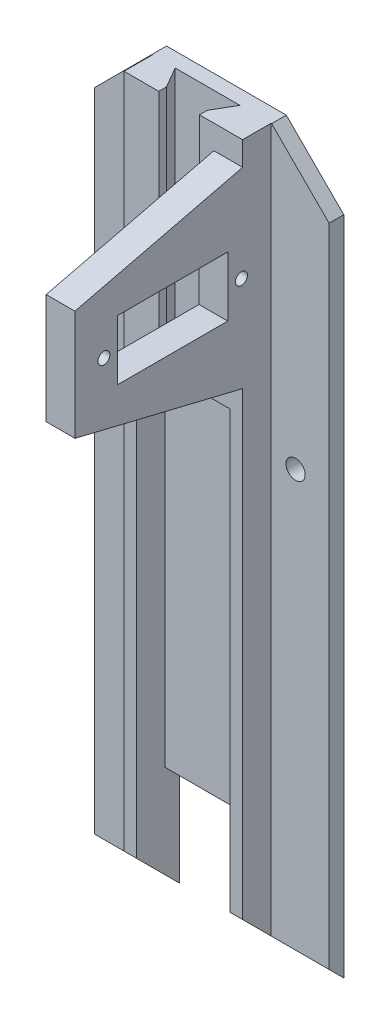
SolidWorks part; units mm, degrees
ref_plane "Front Plane" through (0, 0, 0) normal (0, 0, 1) x (1, 0, 0)
ref_plane "Top Plane" through (0, 0, 0) normal (0, 1, 0) x (1, 0, 0)
ref_plane "Right Plane" through (0, 0, 0) normal (1, 0, 0) x (0, 0, -1)
sketch "Sketch1" plane through (0, 0, 0) normal (0, 0, 1) x (1, 0, 0)
  line L1 (-11.5, 38) -> (11.5, 38)
  line L2 (-11.5, 38) -> (-11.5, -38)
  line L3 (-11.5, -38) -> (11.5, -38)
  line L4 (11.5, 38) -> (11.5, -38)
  line L5 (-11.5, 38) -> (11.5, -38) construction
  line L6 (-11.5, -38) -> (11.5, 38) construction
  point P0 (0, 0)
  dimension "D1" = 76
  dimension "D2" = 23
extrude "Boss-Extrude1" add sketch "Sketch1" along normal blind 8
sketch "Sketch2" plane through (0, -38, 0) normal (0, -1, 0) x (1, 0, 0)
  line L9 (-4.25, 8) -> (4.25, 8)
  line L13 (0, 0) -> (0, 8) construction
  line L14 (-11.5, 8) -> (11.5, 8) construction
  line L15 (-4.25, 8) -> (-4.25, 6.4001)
  line L16 (4.25, 8) -> (4.25, 6.4001)
  line L17 (-6.75, 2.07) -> (6.75, 2.07)
  line L18 (-6.75, 2.07) -> (-4.25, 6.4001)
  line L19 (6.75, 2.07) -> (4.25, 6.4001)
  line L21 (-11.5, 0) -> (11.5, 0) construction
  point P4 (0, 8)
  point P10 (0, 2.07)
  dimension "D1" = 8.5
  dimension "D2" = 2.07
  dimension "D3" = 60
  dimension "D4" = 13.5
extrude "Cut-Extrude2" cut sketch "Sketch2" against normal through all both and the other way through all contours L19 L16 L9 L15 L18 L17
sketch "Sketch3" plane through (0, -38, 0) normal (0, -1, 0) x (1, 0, 0)
  line L0 (4.25, 8) -> (13.25, 8)
  line L1 (13.25, 8) -> (13.25, 0)
  line L2 (13.25, 0) -> (11.5, 0)
  line L3 (11.5, 0) -> (11.5, 8)
  line M7 (11.5, 0) -> (11.5, 8)
  dimension "D1" = 9
extrude "Boss-Extrude2" add sketch "Sketch3" against normal blind 76 contours L2 L1 L0 M7 region at (12.375, -38, 4)
sketch "Sketch4" plane through (13.25, 0, 0) normal (1, 0, 0) x (0, 0, -1)
  line L0 (-8, 38) -> (-8, 33)
  line L6 (-8, 38) -> (-8, -38) construction
  line L7 (-8, 33) -> (-43, 24.5)
  line L8 (-43, 24.5) -> (-43, 1.5)
  line L9 (-43, 1.5) -> (-8, -7)
  line L10 (-8, 33) -> (-8, -7)
  point P5 (-43, 13)
  point P10 (-8, 13)
  line M13 (-8, 38) -> (-8, -38)
  dimension "D1" = 5
  dimension "D2" = 23
  dimension "D3" = 35
  dimension "D4" = 40
extrude "Boss-Extrude3" add sketch "Sketch4" against normal blind 6 contours L8 L9 L7 M13 region at (13.25, 13, 23.9259)
sketch "Sketch5" plane through (13.25, 0, 0) normal (1, 0, 0) x (0, 0, -1)
  line L0 (-43, 24.5) -> (-43, 1.5) construction
  line L1 (-34.1, 19.25) -> (-11.1, 19.25)
  line L2 (-34.1, 19.25) -> (-34.1, 6.75)
  line L3 (-34.1, 6.75) -> (-11.1, 6.75)
  line L4 (-11.1, 19.25) -> (-11.1, 6.75)
  line L5 (-34.1, 19.25) -> (-11.1, 6.75) construction
  line L6 (-34.1, 6.75) -> (-11.1, 19.25) construction
  point P0 (-22.6, 13)
  point P7 (-43, 13)
  dimension "D1" = 23
  dimension "D2" = 12.5
  dimension "D3" = 8.9
extrude "Cut-Extrude3" cut sketch "Sketch5" against normal blind 8
sketch "Sketch6" plane through (13.25, 0, 0) normal (1, 0, 0) x (0, 0, -1)
  line L0 (-43, 13) -> (0, 13) construction
  line L1 (-39.8073, 15.003) -> (-34.1, 15.003)
  line L2 (-39.8073, 15.003) -> (-39.8073, 10.997)
  line L3 (-39.8073, 10.997) -> (-34.1, 10.997)
  line L4 (-34.1, 15.003) -> (-34.1, 10.997)
  line L5 (-39.8073, 15.003) -> (-34.1, 10.997) construction
  line L6 (-39.8073, 10.997) -> (-34.1, 15.003) construction
  line L7 (-43, 24.5) -> (-43, 1.5) construction
  line L8 (0, 38) -> (0, -38) construction
  line L9 (-34.1, 19.25) -> (-34.1, 6.75) construction
  line L10 (-22.6, 19.25) -> (-22.6, 6.75) construction
  line L11 (-11.1, 19.25) -> (-34.1, 19.25) construction
  line L12 (-34.1, 6.75) -> (-11.1, 6.75) construction
  line L13 (-11.1, 15.003) -> (-11.1, 10.997)
  line L14 (-5.3927, 15.003) -> (-11.1, 15.003)
  line L15 (-5.3927, 15.003) -> (-5.3927, 10.997)
  line L16 (-5.3927, 10.997) -> (-11.1, 10.997)
  circle A0 centre (-36.9537, 13) radius 1.25
  circle A1 centre (-8.2463, 13) radius 1.25
  point P0 (-36.9537, 13)
  dimension "D2" = 2.5
  dimension "D1" = 0
extrude "Cut-Extrude4" cut sketch "Sketch6" against normal blind 4 contours A0 | A1
sketch "Sketch7" plane through (0, 0, 0) normal (0, 0, -1) x (-1, 0, 0)
  line L0 (-0.875, 38) -> (-0.875, 23.9968) construction
  line L1 (-13.25, 38) -> (11.5, 38) construction
  line L3 (11.5, 31) -> (17.511, 31) construction
  line L4 (11.5, 38) -> (11.5, -38) construction
  line L5 (11.5, 35) -> (17.511, 35)
  line L7 (11.5, 0) -> (-13.25, 0) construction
  line L8 (-13.25, 38) -> (-13.25, -38) construction
  line L9 (-13.05, 31) -> (-19.061, 31) construction
  line L10 (-13.05, 35) -> (-19.061, 35)
  line L11 (-13.05, 27) -> (-19.061, 27)
  line L12 (-13.05, -31) -> (-19.261, -31) construction
  line L13 (-13.05, -35) -> (-19.061, -35)
  line L14 (-13.05, -27) -> (-19.061, -27)
  line L15 (11.5, -31) -> (17.511, -31) construction
  line L16 (11.5, -35) -> (17.511, -35)
  line L17 (11.5, -27) -> (17.511, -27)
  line L18 (11.5, 35) -> (11.5, 27)
  line L19 (-13.05, 35) -> (-13.05, 27)
  line L20 (-13.05, -27) -> (-13.05, -35)
  line L21 (11.5, -27) -> (11.5, -35)
  line L22 (17.511, 27) -> (11.5, 27)
  arc A1 (17.511, 27) -> (17.511, 35) centre (17.511, 31) ccw
  circle A2 centre (17.511, 31) radius 2
  arc A4 (-19.061, 27) -> (-19.061, 35) centre (-19.061, 31) cw
  circle A5 centre (-19.261, 31) radius 2
  circle A6 centre (-19.261, -31) radius 2
  circle A7 centre (17.511, -31) radius 2
  arc A9 (-19.061, -27) -> (-19.061, -35) centre (-19.261, -31) ccw
  arc A11 (17.511, -27) -> (17.511, -35) centre (17.511, -31) cw
  point P10 (11.5, 31)
  point P23 (-13.05, 31)
  point P35 (-13.05, -31)
  point P41 (11.5, -31)
  dimension "D2" = 4
  dimension "D3" = 4
  dimension "D1" = 3
extrude "Boss-Extrude7" [suppressed] add sketch "Sketch7" against normal blind 3
sketch "Sketch8" plane through (-11.5, 0, 0) normal (-1, 0, 0) x (0, 0, 1)
  line L0 (34.1, 13) -> (0, 13) construction
  line L1 (34.1, 19.25) -> (34.1, 6.75) construction
  line L2 (0, 38) -> (0, -38) construction
  line L3 (8, 38) -> (8, -38) construction
  line L4 (8, 33) -> (8, -7) construction
  line L5 (8, 8.2136) -> (8, 17.7864)
  line L6 (0, 17.7864) -> (8, 17.7864)
  line L7 (0, 8.2136) -> (8, 8.2136)
  line L8 (0, 8.2136) -> (0, 17.7864)
  arc A0 (8, 8.2136) -> (8, 17.7864) centre (11.618, 13) ccw
  circle A1 centre (14, 13) radius 1.5
  point P9 (17.618, 13)
  line M8 (8, -38) -> (8, 38)
  line M14 (0, 38) -> (0, -38)
  dimension "D1" = 6
  dimension "D2" = 3
  dimension "D3" = 14
extrude "Boss-Extrude8" [suppressed] add sketch "Sketch8" along normal blind 3 contours L0 L8 L7 M8 | L0 L5 L6 M14 | A0 L0 A1 M8 | L0 A0 L5 A1
sketch "Sketch9" plane through (-11.5, 0, 0) normal (-1, 0, 0) x (0, 0, 1)
sketch "Sketch10" plane through (0, 0, 43) normal (0, 0, 1) x (1, 0, 0)
  line L0 (7.25, 1.5) -> (13.25, 1.5) construction
  line L1 (13.25, 24.5) -> (13.25, 1.5) construction
  line L2 (13.25, 13) -> (-16.8868, 13) construction
  circle A0 centre (10.25, 5.14) radius 1.5
  circle A1 centre (10.25, 20.86) radius 1.5
  dimension "D1" = 3
  dimension "D2" = 3.64
  dimension "D3" = 3
extrude "Cut-Extrude5" [suppressed] cut sketch "Sketch10" against normal blind 4
fillet "Fillet1" [suppressed] radius 2
sketch "Croquis1" plane through (0, 0, 0) normal (0, 0, -1) x (-1, 0, 0)
  line L1 (-25.375, 38) -> (23.625, 38)
  line L2 (-25.375, 38) -> (-25.375, -112)
  line L3 (-25.375, -112) -> (23.625, -112)
  line L4 (23.625, 38) -> (23.625, -112)
  line L5 (-13.25, 38) -> (11.5, 38) construction
  point P6 (-0.875, 38)
  point P7 (-0.875, 38)
  dimension "D1" = 150
  dimension "D2" = 49
extrude "Saliente-Extruir1" add sketch "Croquis1" along normal blind 1 and the other way blind 2.07
sketch "Croquis2" plane through (0, 0, 2.07) normal (0, 0, 1) x (1, 0, 0)
  line L0 (25.375, 38) -> (25.375, -112) construction
  line L1 (25.375, -12) -> (-23.625, -12)
  line L2 (25.375, -12) -> (25.375, -112)
  line L3 (25.375, -112) -> (-23.625, -112)
  line L4 (-23.625, -12) -> (-23.625, -112)
  line L5 (-23.625, -112) -> (-23.625, 38) construction
  line L6 (7.25, -7) -> (13.25, -7) construction
  line L7 (25.375, -112) -> (-23.625, -112) construction
  point P10 (10.25, -7)
  dimension "D1" = 5
extrude "Cortar-Extruir1" cut sketch "Croquis2" along normal blind 23
sketch "Croquis3" plane through (0, 0, 2.07) normal (0, 0, 1) x (1, 0, 0)
  line L0 (25.375, -112) -> (-23.625, -112) construction
  line L1 (-11.5, -112) -> (13.25, -112)
  line L2 (-11.5, -112) -> (-11.5, -12)
  line L3 (-11.5, -12) -> (13.25, -12)
  line L4 (13.25, -112) -> (13.25, -12)
  line L5 (13.25, -12) -> (6.75, -12) construction
  line L6 (-11.5, -12) -> (-11.5, 38) construction
  line L7 (-23.625, -37) -> (25.375, -37) construction
  line L8 (-23.625, -112) -> (-23.625, 38) construction
  line L9 (25.375, 38) -> (25.375, -112) construction
  point P8 (0.875, -112)
  point P9 (0.875, -37)
extrude "Saliente-Extruir2" add sketch "Croquis3" along normal up to vertex (5.93 mm away) up to point (7.25, -7, 8)
sketch "Croquis4" plane through (0, -112, 0) normal (0, -1, 0) x (1, 0, 0)
  line L0 (-11.5, 8) -> (13.25, 8) construction
  line L1 (-8.875, 8) -> (10.625, 8)
  line L2 (-8.875, 8) -> (-8.875, 2.07)
  line L3 (-8.875, 2.07) -> (10.625, 2.07)
  line L4 (10.625, 8) -> (10.625, 2.07)
  line L5 (25.375, 2.07) -> (13.25, 2.07) construction
  line L6 (-11.5, 5.035) -> (13.25, 5.035) construction
  line L7 (-11.5, 8) -> (-11.5, 2.07) construction
  line L8 (13.25, 8) -> (13.25, 2.07) construction
  point P14 (0.875, 2.07)
  point P15 (0.875, 5.035)
  dimension "D1" = 19.5
extrude "Cortar-Extruir2" cut sketch "Croquis4" against normal blind 100
sketch "Croquis5" plane through (0, 0, 2.07) normal (0, 0, 1) x (1, 0, 0)
  line L7 (10.625, -12) -> (10.625, -112) construction
  line L8 (-8.875, -112) -> (10.625, -112)
  line L9 (-8.875, -112) -> (-8.875, -92.5)
  line L10 (-8.875, -92.5) -> (10.625, -92.5)
  line L11 (10.625, -112) -> (10.625, -92.5)
extrude "Cortar-Extruir4" cut sketch "Croquis5" against normal blind 19
chamfer "Chaflán1" distance 3 angle 45 1 edges at (0.875, -92.5, 2.07)
chamfer "Chaflán2" distance 9 angle 45 2 edges at (11.9375, -112, 8) (-10.1875, -112, 8)
sketch "Croquis6" plane through (0, 0, 2.07) normal (0, 0, 1) x (1, 0, 0)
  line L0 (25.375, -22) -> (18.375, -22) construction
  line L2 (-23.625, -108.93) -> (-23.625, 38) construction
  line L3 (-23.625, 38) -> (25.375, 38) construction
  line L4 (-23.625, -22) -> (-16.625, -22) construction
  line L10 (-16.625, -22) -> (18.375, -22) construction
  line L11 (25.375, 38) -> (25.375, -108.93) construction
  circle A0 centre (-16.625, -22) radius 2
  circle A1 centre (18.375, -22) radius 2
  dimension "D1" = 4
  dimension "D2" = 60
  dimension "D3" = 35
extrude "Cortar-Extruir5" cut sketch "Croquis6" against normal blind 19
chamfer "Chaflán3" distance 12 angle 45 2 edges at (-23.625, 38, 0.535) (25.375, 38, 0.535)
